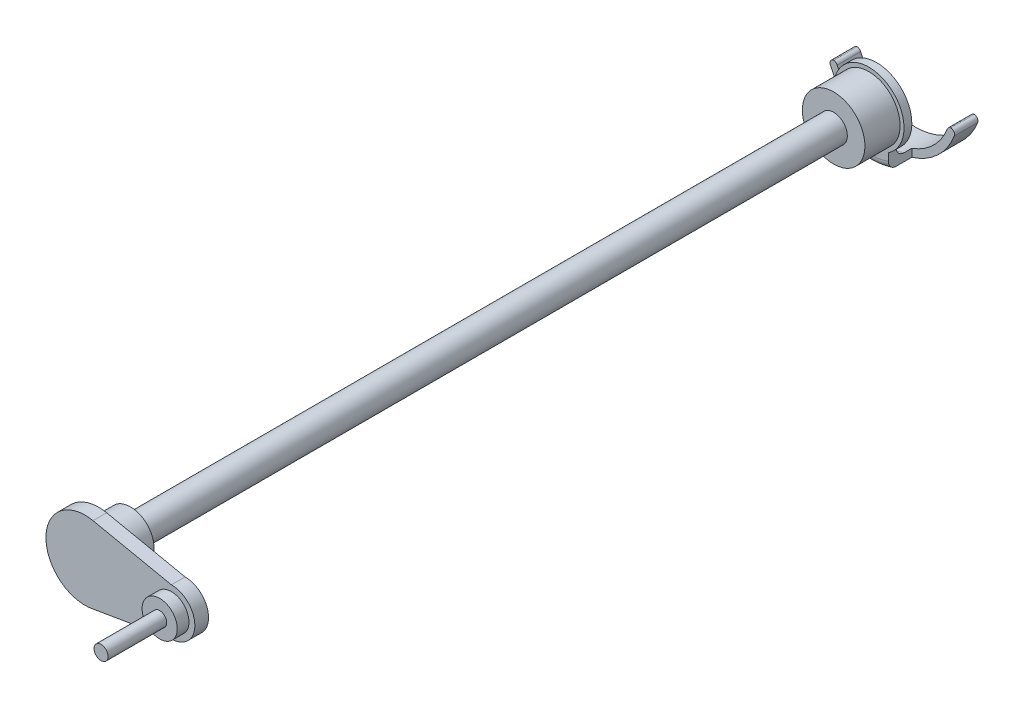
SolidWorks part; units mm, degrees
ref_plane "Alzado" through (0, 0, 0) normal (0, 0, 1) x (1, 0, 0)
ref_plane "Planta" through (0, 0, 0) normal (0, 1, 0) x (1, 0, 0)
ref_plane "Vista lateral" through (0, 0, 0) normal (1, 0, 0) x (0, 0, -1)
sketch "Croquis1" plane through (0, 0, 0) normal (0, 0, 1) x (1, 0, 0)
  circle A0 centre (0, 0) radius 3.5
extrude "Saliente-Extruir1" add sketch "Croquis1" along normal blind 180
sketch "Croquis2" plane through (0, 0, 180) normal (0, 0, 1) x (1, 0, 0)
  circle A0 centre (0, 0) radius 6
extrude "Saliente-Extruir2" add sketch "Croquis2" along normal blind 8 and the other way blind 1
sketch "Croquis3" plane through (0, 0, 188) normal (0, 0, 1) x (1, 0, 0)
  circle A0 centre (0, 0) radius 10
extrude "Saliente-Extruir3" add sketch "Croquis3" along normal blind 3.5
sketch "Croquis4" plane through (0, 0, 191.5) normal (0, 0, 1) x (1, 0, 0)
  line L0 (2.0437, 9.7889) -> (22.0954, 5.6025)
  line L2 (2.0437, -9.7889) -> (22.0954, -6.3975)
  circle A0 centre (0, 0) radius 10 construction
  arc A1 (2.0437, -9.7889) -> (2.0437, 9.7889) centre (0, 0) ccw
  arc A2 (22.0954, -6.3975) -> (22.0954, 5.6025) centre (22.0954, -0.3975) ccw
  point P9 (2.7737, 2.2129)
extrude "Saliente-Extruir4" add sketch "Croquis4" against normal up to surface (3.5 mm away) up to face at (6, 0, 188)
chamfer "Chaflán1" distance 1.5 angle 30 1 edges at (6, 0, 179) first distance on face at (3.5, 0, 179)
sketch "Croquis5" plane through (0, 0, 0) normal (0, 0, -1) x (-1, 0, 0)
  circle A0 centre (0, 0) radius 8
extrude "Saliente-Extruir5" add sketch "Croquis5" along normal blind 9
sketch "Croquis6" plane through (0, 0, -9) normal (0, 0, -1) x (-1, 0, 0)
  circle A0 centre (0, 0) radius 9
extrude "Saliente-Extruir6" add sketch "Croquis6" along normal blind 2
sketch "Croquis7" plane through (0, 0, -11) normal (0, 0, -1) x (-1, 0, 0)
  line L2 (-5, -7.4833) -> (-5, -11.4833)
  line L3 (-5, -11.4833) -> (5, -11.4833)
  line L4 (5, -11.4833) -> (5, -7.4833)
  circle A0 centre (0, 0) radius 9 construction
  circle A2 centre (0, 0) radius 9
  arc A3 (-5, -7.4833) -> (5, -7.4833) centre (0, 0) ccw
  point P8 (0, -9)
  dimension "D1" = 0
extrude "Saliente-Extruir7" add sketch "Croquis7" against normal blind 2
sketch "Croquis12" plane through (0, 0, 191.5) normal (0, 0, 1) x (1, 0, 0)
  circle A0 centre (22.0954, -0.3975) radius 4.5
  arc A1 (22.0954, -6.3975) -> (22.0954, 5.6025) centre (22.0954, -0.3975) ccw construction
  arc A2 (22.0954, -6.3975) -> (22.0954, 5.6025) centre (22.0954, -0.3975) ccw
extrude "Saliente-Extruir11" add sketch "Croquis12" along normal blind 3 contours A0 region at (22.0954, -0.3975, 191.5)
sketch "Croquis13" plane through (0, 0, 194.5) normal (0, 0, 1) x (1, 0, 0)
  circle A0 centre (22.0954, -0.3975) radius 1.8
  circle A1 centre (22.0954, -0.3975) radius 4.5 construction
extrude "Saliente-Extruir12" add sketch "Croquis13" along normal blind 15
sketch "Croquis18" plane through (0, 0, -11) normal (0, 0, -1) x (-1, 0, 0)
  line L0 (-5, -11.4833) -> (-5, -9.4833)
  line L1 (-5, -7.4833) -> (-5, -11.4833) construction
  line L2 (-5, -9.4833) -> (5, -9.4833)
  line L3 (5, -11.4833) -> (5, -7.4833) construction
  line L4 (5, -9.4833) -> (5, -11.4833)
  line L5 (5, -11.4833) -> (-5, -11.4833)
extrude "Saliente-Extruir16" add sketch "Croquis18" along normal blind 4
sketch "Croquis19" plane through (0, 0, -15) normal (0, 0, -1) x (-1, 0, 0)
  line L0 (14.3285, 0) -> (16.3186, 0)
  line L1 (-16.3186, 0) -> (-14.3285, 0)
  arc A0 (-16.3186, 0) -> (16.3186, 0) centre (0, 4.7648) ccw
  arc A1 (-14.3285, 0) -> (14.3285, 0) centre (0, 4.7648) ccw
  circle A2 centre (0, 4.7648) radius 17 construction
  circle A3 centre (0, 4.7648) radius 15.0999 construction
extrude "Saliente-Extruir17" add sketch "Croquis19" along normal blind 6
sketch "Croquis20" plane through (0, 0, -15) normal (0, 0, -1) x (-1, 0, 0)
  line L1 (5, -9.4833) -> (-5, -9.4833)
  line L2 (5, -9.4833) -> (-5, -9.4833)
  arc A1 (-5, -9.4833) -> (5, -9.4833) centre (0, 4.7648) ccw
  arc A2 (-5, -9.4833) -> (5, -9.4833) centre (0, 4.7648) ccw
  dimension "D1" = 0
extrude "Cortar-Extruir3" cut sketch "Croquis20" against normal up to surface (4 mm away) up to face at (-1.25, -4.3625, -11)
sketch "Croquis21" plane through (0, 0, -15) normal (0, 0, 1) x (1, 0, 0)
  line L1 (5, -11.4833) -> (-5, -11.4833)
  line L2 (5, -11.4833) -> (-5, -11.4833)
  arc A1 (-5, -11.4833) -> (5, -11.4833) centre (0, 4.7648) ccw
  arc A2 (-5, -11.4833) -> (5, -11.4833) centre (0, 4.7648) ccw
  dimension "D1" = 0
extrude "Saliente-Extruir18" add sketch "Croquis21" along normal up to surface (6 mm away) up to face at (-8, 0, -9)
fillet "Redondeo7" radius 2 2 edges at (0, -12.2352, -9)
fillet "Redondeo8" radius 1 4 edges at (-16.3186, 0, -18) (-14.3285, 0, -18) (16.3186, 0, -18) (14.3285, 0, -18)
